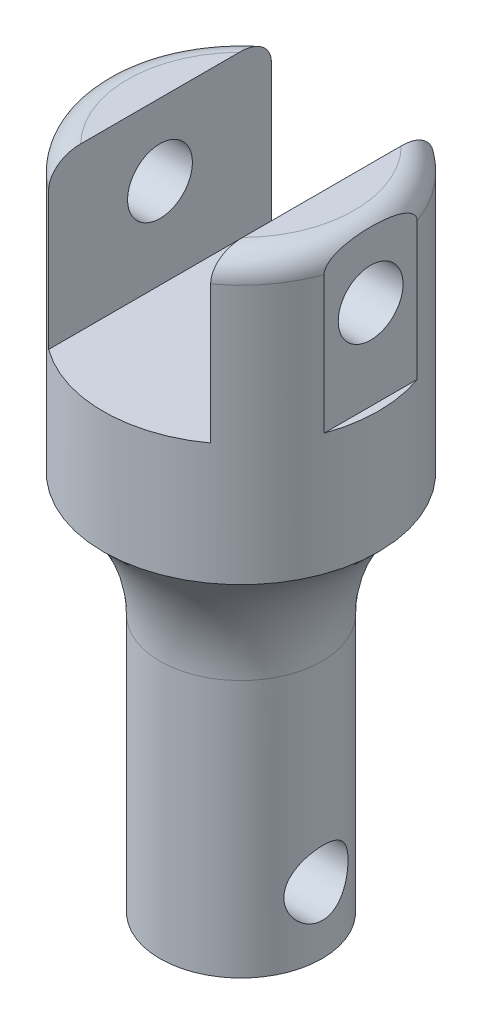
SolidWorks part; units mm, degrees
ref_plane "Спереди" through (0, 0, 0) normal (0, 0, 1) x (1, 0, 0)
ref_plane "Сверху" through (0, 0, 0) normal (0, 1, 0) x (1, 0, 0)
ref_plane "Справа" through (0, 0, 0) normal (1, 0, 0) x (0, 0, -1)
sketch "Эскиз1" plane through (0, 0, 0) normal (0, 1, 0) x (1, 0, 0)
  circle A0 centre (0, 0) radius 17
extrude "Вытянуть1" add sketch "Эскиз1" along normal blind 35 from offset 15
sketch "Эскиз2" plane through (0, -15, 0) normal (0, -1, 0) x (1, 0, 0)
  circle A0 centre (0, 0) radius 10
extrude "Вытянуть2" add sketch "Эскиз2" along normal blind 47
fillet "Скругление3" radius 3 1 edges at (0, 20, 17)
fillet "Скругление4" radius 20 1 edges at (0, -15, 10)
sketch "Эскиз4" plane through (0, 0, 0) normal (0, 0, 1) x (1, 0, 0)
  line L1 (-10, 21.1336) -> (10, 21.1336)
  line L2 (-10, 21.1336) -> (-10, 0)
  line L3 (-10, 0) -> (10, 0)
  line L4 (10, 21.1336) -> (10, 0)
extrude "Вырез-Вытянуть2" cut sketch "Эскиз4" against normal mid plane 70
sketch "Эскиз5" plane through (0, 0, 0) normal (1, 0, 0) x (0, 0, -1)
  circle A0 centre (0, 11.1289) radius 4
extrude "Вырез-Вытянуть3" cut sketch "Эскиз5" against normal mid plane 70
sketch "Эскиз6" plane through (0, 0, 0) normal (1, 0, 0) x (0, 0, -1)
  line L1 (-7.5, 0.0513) -> (7.5, 0.0513)
  line L2 (-7.5, 0.0513) -> (-7.5, 20.6248)
  line L3 (-7.5, 20.6248) -> (7.5, 20.6248)
  line L4 (7.5, 0.0513) -> (7.5, 20.6248)
  point P0 (0, 11.1289)
extrude "Вырез-Вытянуть4" cut sketch "Эскиз6" against normal blind 4 from offset 20
sketch "Эскиз7" plane through (0, 0, 0) normal (1, 0, 0) x (0, 0, -1)
  line L1 (-10, 2.6289) -> (10, 2.6289)
  line L2 (-10, 2.6289) -> (-10, 20.788)
  line L3 (-10, 20.788) -> (10, 20.788)
  line L4 (10, 2.6289) -> (10, 20.788)
extrude "Вырез-Вытянуть5" cut sketch "Эскиз7" along normal blind 4 from offset 20
sketch "Эскиз8" plane through (0, 0, 0) normal (1, 0, 0) x (0, 0, -1)
  circle A0 centre (0.0825, -53.9269) radius 4
extrude "Вырез-Вытянуть6" cut sketch "Эскиз8" against normal mid plane 70
